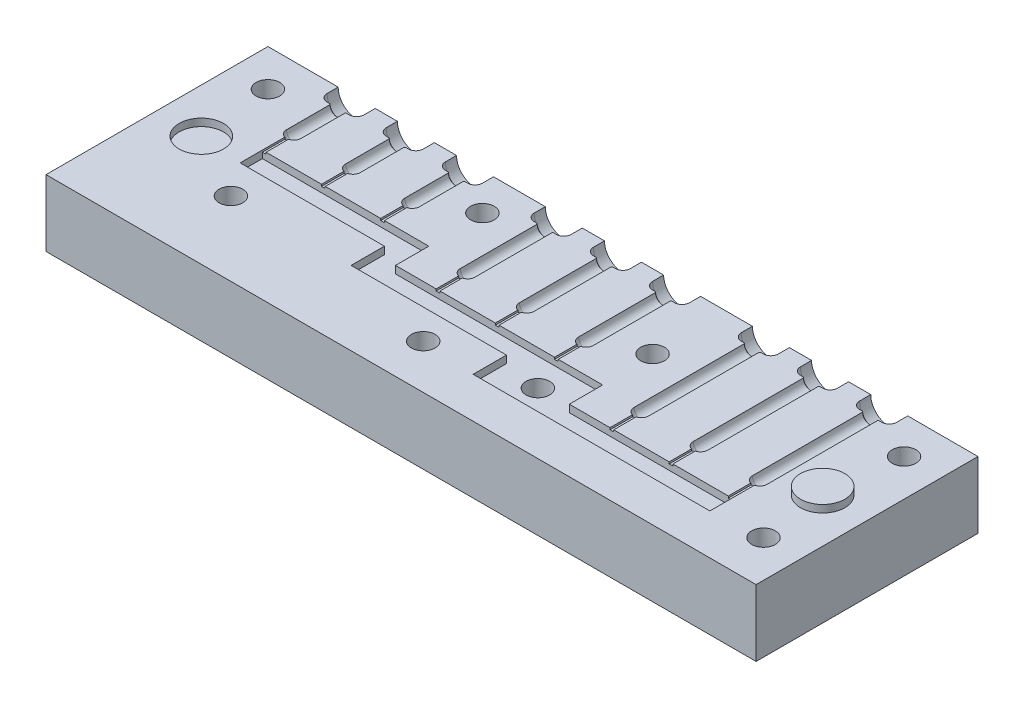
SolidWorks part; units mm, degrees
ref_plane "Ebene vorne" through (0, 0, 0) normal (0, 0, 1) x (1, 0, 0)
ref_plane "Ebene oben" through (0, 0, 0) normal (0, 1, 0) x (1, 0, 0)
ref_plane "Ebene rechts" through (0, 0, 0) normal (1, 0, 0) x (0, 0, -1)
sketch "Skizze1" plane through (0, 0, 0) normal (0, 1, 0) x (1, 0, 0)
  line L1 (0, 0) -> (96, 0)
  line L2 (0, 0) -> (0, 30)
  line L3 (0, 30) -> (96, 30)
  line L4 (96, 0) -> (96, 30)
  dimension "D1" = 96
  dimension "D2" = 30
extrude "Aufsatz-Linear austragen1" add sketch "Skizze1" along normal blind 9
sketch "Skizze2" plane through (0, 0, -30) normal (0, 0, -1) x (-1, 0, 0)
  line L0 (-96, 9) -> (0, 9) construction
  line L1 (-12, 9) -> (-20, 9) construction
  line L2 (-20, 9) -> (-28, 9) construction
  line L3 (-40, 9) -> (-48, 9) construction
  line L4 (-48, 9) -> (-56, 9) construction
  line L5 (-68, 9) -> (-76, 9) construction
  line L6 (-76, 9) -> (-84, 9) construction
  circle A0 centre (-12, 9) radius 1
  circle A1 centre (-20, 9) radius 1
  circle A2 centre (-28, 9) radius 1
  circle A3 centre (-40, 9) radius 1
  circle A4 centre (-48, 9) radius 1
  circle A5 centre (-56, 9) radius 1
  circle A6 centre (-68, 9) radius 1
  circle A7 centre (-76, 9) radius 1
  circle A8 centre (-84, 9) radius 1
  dimension "D1" = 2
  dimension "D2" = 8
  dimension "D3" = 12
  dimension "D5" = 12
  dimension "D4" = 3
extrude "Schnitt-Linear austragen1" cut sketch "Skizze2" against normal blind 9.5 contours A0 | A1 | A2
extrude "Schnitt-Linear austragen2" cut sketch "Skizze2<4>" against normal blind 14 contours A3 | A4 | A5
sketch "Skizze2<4>" plane through (0, 0, -30) normal (0, 0, -1) x (-1, 0, 0) same geometry as "Skizze2"
extrude "Schnitt-Linear austragen3" cut sketch "Skizze2<5>" against normal blind 18.5 contours A6 | A7 | A8
sketch "Skizze2<5>" plane through (0, 0, -30) normal (0, 0, -1) x (-1, 0, 0) same geometry as "Skizze2"
sketch "Skizze4" plane through (0, 0, -30) normal (0, 0, -1) x (-1, 0, 0)
  circle A0 centre (-12, 9) radius 2.5
  circle A1 centre (-20, 9) radius 2.5
  circle A2 centre (-28, 9) radius 2.5
  arc A3 (-13, 9) -> (-11, 9) centre (-12, 9) ccw construction
  arc A4 (-21, 9) -> (-19, 9) centre (-20, 9) ccw construction
  arc A5 (-29, 9) -> (-27, 9) centre (-28, 9) ccw construction
  circle A6 centre (-40, 9) radius 2.5
  circle A7 centre (-48, 9) radius 2.5
  circle A8 centre (-56, 9) radius 2.5
  circle A9 centre (-68, 9) radius 2.5
  circle A10 centre (-76, 9) radius 2.5
  circle A11 centre (-84, 9) radius 2.5
  dimension "D1" = 5
  dimension "D2" = 3
extrude "Schnitt-Linear austragen4" cut sketch "Skizze4" against normal blind 2.5
fillet "Verrundung1" radius 1 18 edges at (84, 6.5, -27.5) (76, 6.5, -27.5) (68, 6.5, -27.5) (56, 6.5, -27.5) (48, 6.5, -27.5) (40, 6.5, -27.5) (28, 6.5, -27.5) (20, 6.5, -27.5) (12, 6.5, -27.5) (12, 8, -20.5) (20, 8, -20.5) (28, 8, -20.5) (40, 8, -16) (48, 8, -16) (56, 8, -16) (68, 8, -11.5) (76, 8, -11.5) (84, 8, -11.5)
chamfer "Fase1" distance 0.1 angle 45 9 edges at (20, 8, -27.5) (12, 8, -27.5) (28, 8, -27.5) (56, 8, -27.5) (48, 8, -27.5) (40, 8, -27.5) (68, 8, -27.5) (76, 8, -27.5) (84, 8, -27.5)
sketch "Skizze5" plane through (0, 9, 0) normal (0, 1, 0) x (1, 0, 0)
  line L0 (12, 20.5) -> (12, 17.5) construction
  line L1 (40, 16) -> (40, 13) construction
  line L2 (11.75, 17.5) -> (12, 17.5)
  line L3 (11.75, 21.5) -> (11.75, 17.5)
  line L4 (12.25, 17.5) -> (12, 17.5)
  line L5 (39.75, 13) -> (40, 13)
  line L6 (39.75, 17) -> (39.75, 13)
  line L7 (40, 13) -> (40.25, 13)
  line L8 (11.75, 21.5) -> (12.25, 21.5)
  line L9 (68, 11.5) -> (68, 8.5) construction
  line L10 (19.75, 17.5) -> (20, 17.5)
  line L11 (40.25, 16) -> (40.25, 13) construction
  line L12 (39.75, 16) -> (39.75, 13) construction
  line L13 (39.75, 17) -> (40.25, 17)
  line L14 (67.75, 8.5) -> (68, 8.5)
  line L15 (67.75, 12.5) -> (67.75, 8.5)
  line L16 (68, 8.5) -> (68.25, 8.5)
  line L17 (67.75, 11.5) -> (67.75, 8.5) construction
  line L18 (12.25, 21.5) -> (12.25, 17.5)
  line L19 (40.25, 17) -> (40.25, 13)
  line L20 (19.75, 21.5) -> (19.75, 17.5)
  line L21 (20.25, 17.5) -> (20, 17.5)
  line L22 (68.25, 11.5) -> (68.25, 8.5) construction
  line L23 (67.75, 12.5) -> (68.25, 12.5)
  line L24 (68.25, 12.5) -> (68.25, 8.5)
  line L25 (47.75, 13) -> (48, 13)
  line L26 (47.75, 17) -> (47.75, 13)
  line L27 (12.25, 20.5) -> (12.25, 17.5) construction
  line L28 (11.75, 20.5) -> (11.75, 17.5) construction
  line L29 (19.75, 21.5) -> (20.25, 21.5)
  line L30 (20.25, 21.5) -> (20.25, 17.5)
  line L31 (20, 20.5) -> (20, 17.5) construction
  line L32 (27.75, 17.5) -> (28, 17.5)
  line L33 (27.75, 21.5) -> (27.75, 17.5)
  line L34 (28.25, 17.5) -> (28, 17.5)
  line L35 (27.75, 21.5) -> (28.25, 21.5)
  line L36 (28.25, 21.5) -> (28.25, 17.5)
  line L37 (28, 20.5) -> (28, 17.5) construction
  line L38 (48, 13) -> (48.25, 13)
  line L39 (47.75, 17) -> (48.25, 17)
  line L40 (48.25, 17) -> (48.25, 13)
  line L41 (48, 16) -> (48, 13) construction
  line L42 (55.75, 13) -> (56, 13)
  line L43 (55.75, 17) -> (55.75, 13)
  line L44 (56, 13) -> (56.25, 13)
  line L45 (55.75, 17) -> (56.25, 17)
  line L46 (56.25, 17) -> (56.25, 13)
  line L47 (56, 16) -> (56, 13) construction
  line L48 (75.75, 8.5) -> (76, 8.5)
  line L49 (75.75, 12.5) -> (75.75, 8.5)
  line L50 (76, 8.5) -> (76.25, 8.5)
  line L51 (75.75, 12.5) -> (76.25, 12.5)
  line L52 (76.25, 12.5) -> (76.25, 8.5)
  line L53 (76, 11.5) -> (76, 8.5) construction
  line L54 (83.75, 8.5) -> (84, 8.5)
  line L55 (83.75, 12.5) -> (83.75, 8.5)
  line L56 (84, 8.5) -> (84.25, 8.5)
  line L57 (83.75, 12.5) -> (84.25, 12.5)
  line L58 (84.25, 12.5) -> (84.25, 8.5)
  line L59 (84, 11.5) -> (84, 8.5) construction
  dimension "D1" = 3
  dimension "D2" = 0.5
  dimension "D4" = 8
  dimension "D5" = 3
  dimension "D6" = 8
  dimension "D8" = 8
  dimension "D3" = 3
  dimension "D7" = 3
extrude "Schnitt-Linear austragen5" cut sketch "Skizze5" against normal blind 0.25
sketch "Skizze6" plane through (0, 9, 0) normal (0, 1, 0) x (1, 0, 0)
  line L0 (34.25, 17.5) -> (11.75, 17.5)
  line L1 (34.25, 13) -> (62.25, 13)
  line L2 (34.25, 17.5) -> (34.25, 13)
  line L3 (28.25, 17.5) -> (28.25, 20.5318) construction
  line L4 (47.75, 13) -> (48.25, 13) construction
  line L5 (62.25, 13) -> (62.25, 8.5)
  line L6 (62.25, 8.5) -> (84.25, 8.5)
  line L7 (11.75, 17.5) -> (11.75, 14.5)
  line L8 (11.75, 14.5) -> (31.25, 14.5)
  line L9 (31.25, 14.5) -> (31.25, 10)
  line L10 (31.25, 10) -> (52.25, 10)
  line L11 (52.25, 10) -> (52.25, 5.5)
  line L12 (52.25, 5.5) -> (84.25, 5.5)
  line L13 (84.25, 5.5) -> (84.25, 8.5)
  line L14 (62.25, 8.5) -> (52.25, 8.5) construction
  line L15 (34.25, 13) -> (34.25, 10) construction
  line L16 (31.25, 14.5) -> (34.25, 14.5) construction
  line L17 (56.25, 13) -> (56.25, 16.0318) construction
  dimension "D1" = 6
  dimension "D2" = 3
  dimension "D3" = 6
  dimension "D4" = 10
extrude "Schnitt-Linear austragen6" cut sketch "Skizze6" against normal blind 1
sketch "Skizze7" plane through (0, 8, 0) normal (0, 1, 0) x (1, 0, 0)
  line L0 (52.25, 10) -> (62.25, 8.5) construction
  circle A0 centre (57.25, 9.25) radius 1.6
  dimension "D1" = 3.2
extrude "Schnitt-Linear austragen7" cut sketch "Skizze7" against normal up to next
hole_wizard "Durchgangsloch für M31" positions "Skizze9" profile "Skizze8" hole size "M3" standard "DIN" end condition through all
sketch "Skizze9" plane through (0, 9, 0) normal (0, 1, 0) x (1, 0, 0)
  line L0 (0, 30) -> (0, 0) construction
  line L1 (9.5, 30) -> (0, 30) construction
  line L2 (5, 25) -> (34, 25)
  line L5 (34, 25) -> (91, 25)
  line L7 (96, 0) -> (96, 30) construction
  line L8 (91, 6) -> (45, 6)
  line L9 (45, 6) -> (15, 6)
  line L10 (15, 6) -> (15, 10)
  line L12 (0, 0) -> (96, 0) construction
  point P0 (34, 25)
  point P2 (62, 20)
  point P4 (91, 25)
  point P6 (91, 6)
  point P8 (15, 10)
  point P10 (5, 25)
  point P34 (45, 6)
  dimension "D1" = 5
  dimension "D2" = 5
  dimension "D3" = 34
  dimension "D4" = 5
  dimension "D5" = 34
  dimension "D6" = 5
  dimension "D7" = 15
  dimension "D8" = 5
  dimension "D9" = 6
  dimension "D10" = 4
  dimension "D11" = 30
sketch "Skizze8" plane through (34, 9, -25) normal (1, 0, 0) x (0, 0, 1)
  line L0 (0, 0) -> (0, 9)
  line L1 (0, 9) -> (1.6, 9)
  line L2 (1.6, 9) -> (1.6, 0)
  line L5 (1.6, 0) -> (0, 0)
  line L11 (0, -6.35) -> (0, 107.95) construction
  dimension "Bohrerdurchmesser" = 3.2
  dimension "Bohrungstiefe" = 9
sketch "Skizze10" plane through (0, 9, 0) normal (0, 1, 0) x (1, 0, 0)
  line L0 (0, 15) -> (6, 15) construction
  line L1 (0, 30) -> (0, 0) construction
  line L2 (6, 15) -> (90, 15) construction
  line L3 (90, 15) -> (96, 15) construction
  line L4 (96, 0) -> (96, 30) construction
  circle A0 centre (6, 15) radius 3
  circle A1 centre (90, 15) radius 3
  dimension "D1" = 6
  dimension "D2" = 6
extrude "Schnitt-Linear austragen8" cut sketch "Skizze10" against normal blind 1 contours A0
extrude "Aufsatz-Linear austragen2" add sketch "Skizze10<3>" along normal blind 1 contours A1 region at (90, 9, -15)
sketch "Skizze10<3>" plane through (0, 9, 0) normal (0, 1, 0) x (1, 0, 0) same geometry as "Skizze10"
